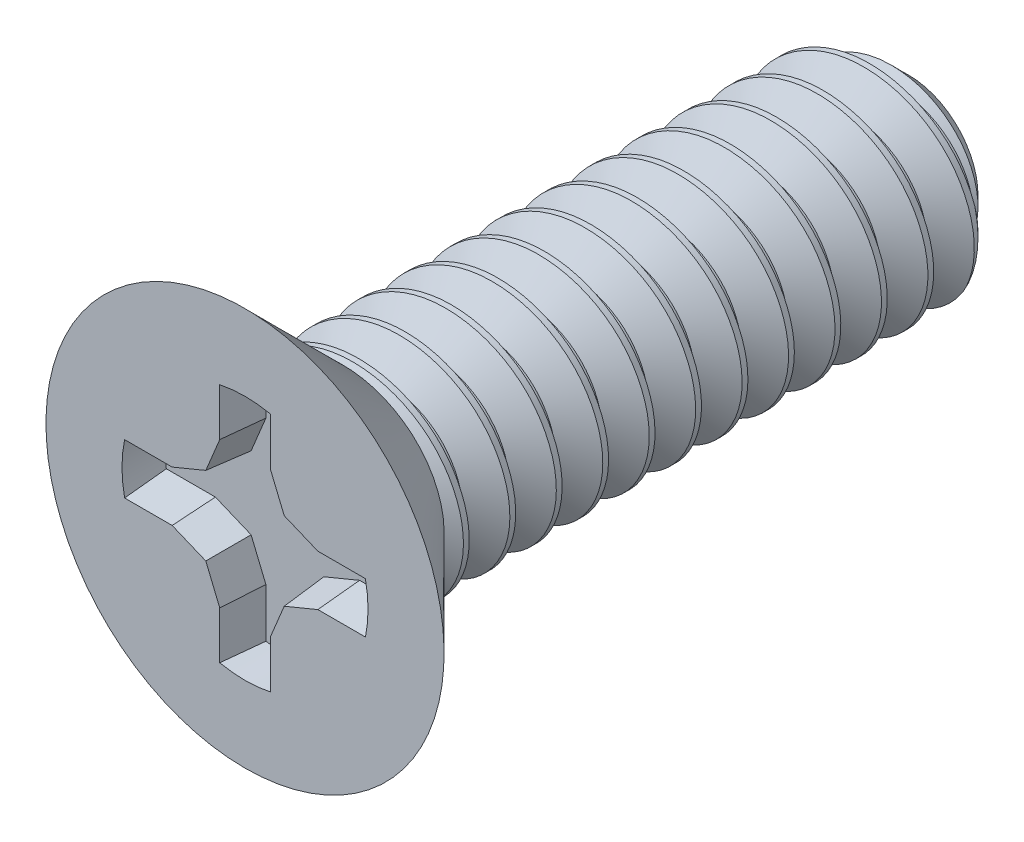
SolidWorks part; units mm, degrees
ref_plane "Front Plane" through (0, 0, 0) normal (0, 0, 1) x (1, 0, 0)
ref_plane "Top Plane" through (0, 0, 0) normal (0, 1, 0) x (1, 0, 0)
ref_plane "Right Plane" through (0, 0, 0) normal (1, 0, 0) x (0, 0, -1)
sketch "Sketch1" plane through (0, 0, 0) normal (1, 0, 0) x (0, 0, -1)
  line L0 (0, 0) -> (-0.96, 0) construction
  line L1 (-0.96, 1.5) -> (-0.96, -1.5) construction
  line L2 (-0.96, 1.5) -> (0, 0.54) construction
  line L3 (-0.96, -1.5) -> (0, -0.54) construction
  line L4 (0, 0.8) -> (0, -0.8) construction
  line L5 (0, 0) -> (4.04, 0) construction
  line L6 (0, 0.8) -> (0.35, 0.8) construction
  line L7 (0, 0.8) -> (-0.26, 0.8) construction
  line L8 (4.04, 0.54) -> (4.04, -0.54) construction
  point P6 (-0.96, 0)
  point P11 (0, 0)
  point P16 (-0.26, 0.8)
  point P17 (2.815, -0.8)
  point P20 (4.04, 0)
  point P21 (-0.48, 0)
  point P22 (2.815, -0.54)
  point P23 (4.04, -0.54)
  point P25 (4.04, 0.54)
  dimension "Head Height" = 0.96
  dimension "Head Diameter" = 3
  dimension "Countersink Angle" = 90
  dimension "Thread OD" = 1.6
  dimension "Length" = 5
  dimension "Thread Pitch" = 0.35
  dimension "D1" = 1.225
sketch "Sketch2" plane through (0, 0, 0) normal (0, 0, 1) x (1, 0, 0)
  line L0 (0.1905, 0.9271) -> (-0.1905, 0.9271) construction
  circle A0 centre (0, 0) radius 0.9271 construction
  point P3 (0, 0.9271)
  point P7 (0, 0.9271)
  dimension "Drive Dia" = 1.8542
  dimension "Drive Width" = 0.381
sketch "Sketch3" plane through (0, 0, 0) normal (1, 0, 0) x (0, 0, -1)
  line L0 (-0.96, 0) -> (-0.96, 1.5)
  line L1 (-0.96, 1.5) -> (-0.26, 0.8)
  line L2 (-0.96, 1.5) -> (0, 0.54) construction
  line L3 (0, 0.8) -> (0.35, 0.8) construction
  line L4 (-0.96, 0) -> (-0.26, 0)
  line L5 (0, 0) -> (-0.96, 0) construction
  line L6 (-0.26, 0) -> (-0.26, 0.8)
revolve "Revolve1" add sketch "Sketch3" angle 360 about L4
sketch "Sketch5" plane through (0, 0, 0) normal (1, 0, 0) x (0, 0, -1)
  line L0 (4.04, 0) -> (-0.26, 0)
  line L1 (0, 0) -> (4.04, 0) construction
  line L2 (-0.26, 0) -> (-0.26, 0.8)
  line L3 (-0.26, 0.8) -> (3.7635, 0.8)
  line L4 (3.7635, 0.8) -> (4.04, 0.5235)
  line L5 (4.04, 0.5235) -> (4.04, 0)
  line L6 (3.7635, 0.8) -> (4.04, 0.8) construction
  line L7 (4.04, 0.8) -> (4.04, 0.5235) construction
  line L8 (0, 0.8) -> (0.35, 0.8) construction
  line L9 (-0.26, -0.8) -> (-0.26, 0.8) construction
  dimension "D1" = 0.2765
revolve "Revolve2" add sketch "Sketch5" angle 360 about L0
sketch "Sketch4" plane through (0, 0, 0.96) normal (0, 0, 1) x (1, 0, 0)
  line L0 (0, 0) -> (0, 0.9271)
  line L1 (0, 0) -> (0.9271, 0)
  line L2 (0, 0) -> (0.5489, 0.5489) construction
  line L3 (0.1905, 0.9073) -> (0.1905, 0.5489)
  line L4 (0.1905, 0.5489) -> (0.1905, 0.1905) construction
  line L5 (0.5489, 0.1905) -> (0.1905, 0.1905) construction
  line L6 (0.9073, 0.1905) -> (0.5489, 0.1905)
  line L7 (0.1905, 0.5489) -> (0.2955, 0.2955)
  line L8 (0.2955, 0.2955) -> (0.5489, 0.1905)
  line L9 (0, 0.9271) -> (0, 1.5) construction
  line L10 (0, 1.5) -> (0, -1.5) construction
  circle A0 centre (0, 0) radius 0.9271 construction
  arc A1 (0, 0.9271) -> (0.1905, 0.9073) centre (0, 0) cw
  arc A2 (0.9271, 0) -> (0.9073, 0.1905) centre (0, 0) ccw
  arc A3 (0.5489, 0.1905) -> (0.1905, 0.5489) centre (0.5489, 0.5489) cw construction
  circle A4 centre (0, 0) radius 1.5 construction
  point P8 (0.2955, 0.2955)
  point P22 (0, -0.9271)
  point P23 (0, 0.9271)
  dimension "D1" = 0.5729
extrude "Cut-Extrude1" cut sketch "Sketch4" against normal blind 0.32 contours L1 A2 L6 L8 L7 L3 A1 L0
pattern_circular "CirPattern1" count 4 over 360 about axis through (0, 0, 0) along (0, 0, 1) of "Cut-Extrude1"
draft "Draft2" type of draft neutral plane draft angle 5 faces to draft 16 face at (-0.7281, 0.1905, 0.8) face at (-0.4222, 0.243, 0.8) face at (-0.243, 0.4222, 0.8) face at (-0.1905, 0.7281, 0.8) face at (0.1905, 0.7281, 0.8) face at (0.243, 0.4222, 0.8) face at (0.4222, 0.243, 0.8) face at (0.7281, 0.1905, 0.8) face at (0.7281, -0.1905, 0.8) face at (0.4222, -0.243, 0.8) face at (0.243, -0.4222, 0.8) face at (0.1905, -0.7281, 0.8) face at (-0.1905, -0.7281, 0.8) face at (-0.243, -0.4222, 0.8) face at (-0.4222, -0.243, 0.8) face at (-0.7281, -0.1905, 0.8) neutral plane through (0, 0, 0.96) neutral plane normal (0, 0, 1) parameters "D1"=5
ref_plane "Plane1" through (0, 0, 0.26) normal (0, 0, -1) x (-1, 0, 0)
split "Split1" trim tools "Plane1" bodies to split 107 105 resulting bodies 108 109
sketch "Sketch6" plane through (0, 0, -4.04) normal (0, 0, 1) x (1, 0, 0)
  circle A1 centre (0, 0) radius 0.8
  circle A2 centre (0, 0) radius 0.8
  dimension "D1" = 0
curve "Helix/Spiral1" pitch 0.35 height 5 turns 14.2857
sketch "Sketch7" plane through (0, 0, 0) normal (1, 0, 0) x (0, 0, -1)
  line L0 (4.0181, 0.8379) -> (4.3681, 0.8379) construction
  line L1 (4.0181, 0.8379) -> (4.1931, 0.5348) construction
  line L2 (4.1931, 0.5348) -> (4.3681, 0.8379) construction
  line L3 (4.1712, 0.5727) -> (4.215, 0.5727) construction
  line L4 (4.04, 0.8) -> (4.3463, 0.8) construction
  line L5 (4.1931, 0.8) -> (4.1931, 0.8379) construction
  line L6 (4.1931, 0.5727) -> (4.1931, 0.5348) construction
  line L7 (4.1931, 0.8189) -> (4.0291, 0.8189) construction
  line L10 (4.215, 0.5727) -> (4.1712, 0.5727)
  line L11 (4.0291, 0.8189) -> (4.1712, 0.5727)
  line L12 (4.0291, 0.8189) -> (4.3572, 0.8189)
  line L13 (4.3572, 0.8189) -> (4.215, 0.5727)
  dimension "D1" = 0.35
  dimension "D2" = 0.0437
sweep "Cut-Sweep1" cut profiles "Sketch7" path "Helix/Spiral1" align with end faces yes
combine bodies "Combine1" operation type add bodies to combine 109 110
ref_plane "Plane2" through (0, 0, 0.26) normal (0, 0, 1) x (1, 0, 0)
sketch "Sketch8" plane through (0, 0, 0.26) normal (0, 0, 1) x (1, 0, 0)
  circle A0 centre (0, 0) radius 0.8
extrude "Boss-Extrude1" add sketch "Sketch8" against normal up to vertex (0.26 mm away) draft 45 up to point (0, 0.54, 0)
equation "\"D1@Sketch5\" = \"Thread Pitch@Sketch1\" * .79"
equation "\"D4@Helix/Spiral1\" = \"Thread Pitch@Sketch1\""
equation "\"D3@Helix/Spiral1\"=\"Length@Sketch1\""
equation "\"D1@Sketch7\" = \"Thread Pitch@Sketch1\""
equation "\"D2@Sketch7\" = \"Thread Pitch@Sketch1\" / 8"
equation "\"D1@Sketch1\"=\"Thread Pitch@Sketch1\"*3.5"
equation "\"D1@Cut-Extrude1\"=\"Head Height@Sketch1\"/3"
